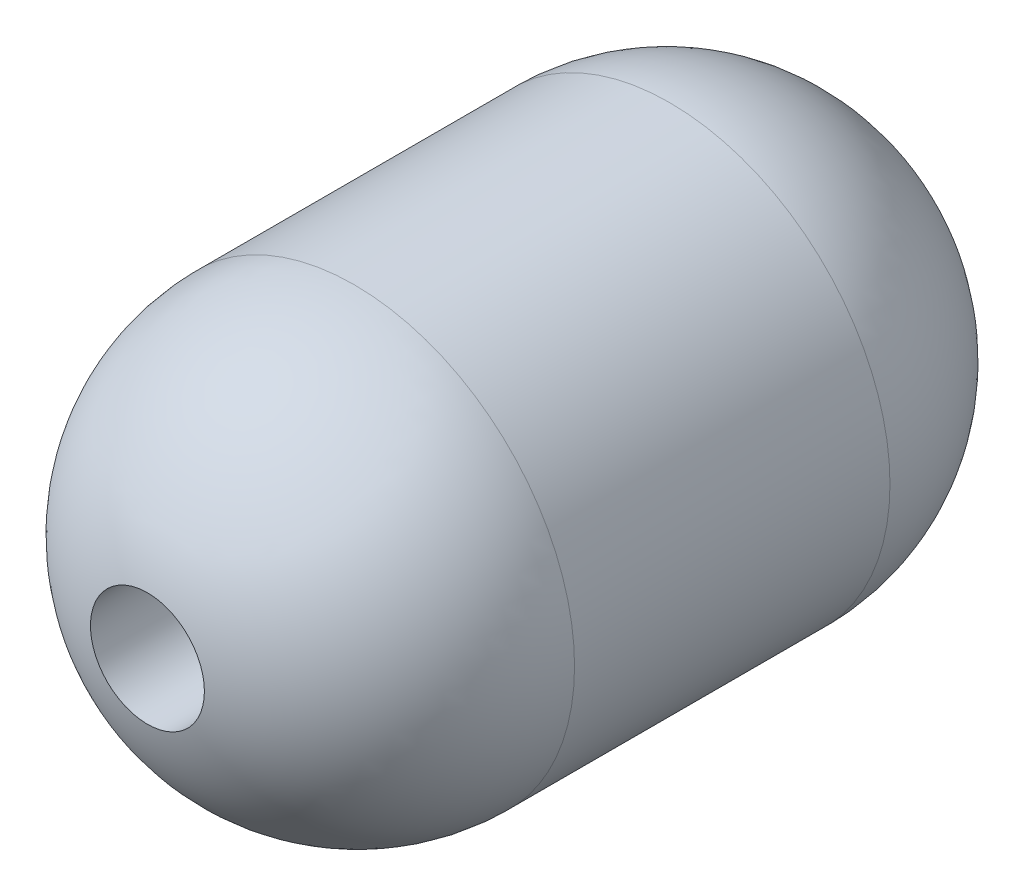
SolidWorks part; units mm, degrees
ref_plane "Plan de face" through (0, 0, 0) normal (0, 0, 1) x (1, 0, 0)
ref_plane "Plan de dessus" through (0, 0, 0) normal (0, 1, 0) x (1, 0, 0)
ref_plane "Plan de droite" through (0, 0, 0) normal (1, 0, 0) x (0, 0, -1)
sketch "Esquisse1" plane through (0, 0, 0) normal (0, 0, 1) x (1, 0, 0)
  circle A0 centre (0, 0) radius 2.9
  circle A1 centre (0, 0) radius 0.75
  dimension "D1" = 5.8
  dimension "D2" = 1.5
extrude "Boss.-Extru.1" add sketch "Esquisse1" along normal blind 9.6
fillet "Congé1" radius 2.8 1 edges at (2.9, 0, 9.6)
fillet "Congé2" radius 2.8 1 edges at (2.9, 0, 0)
